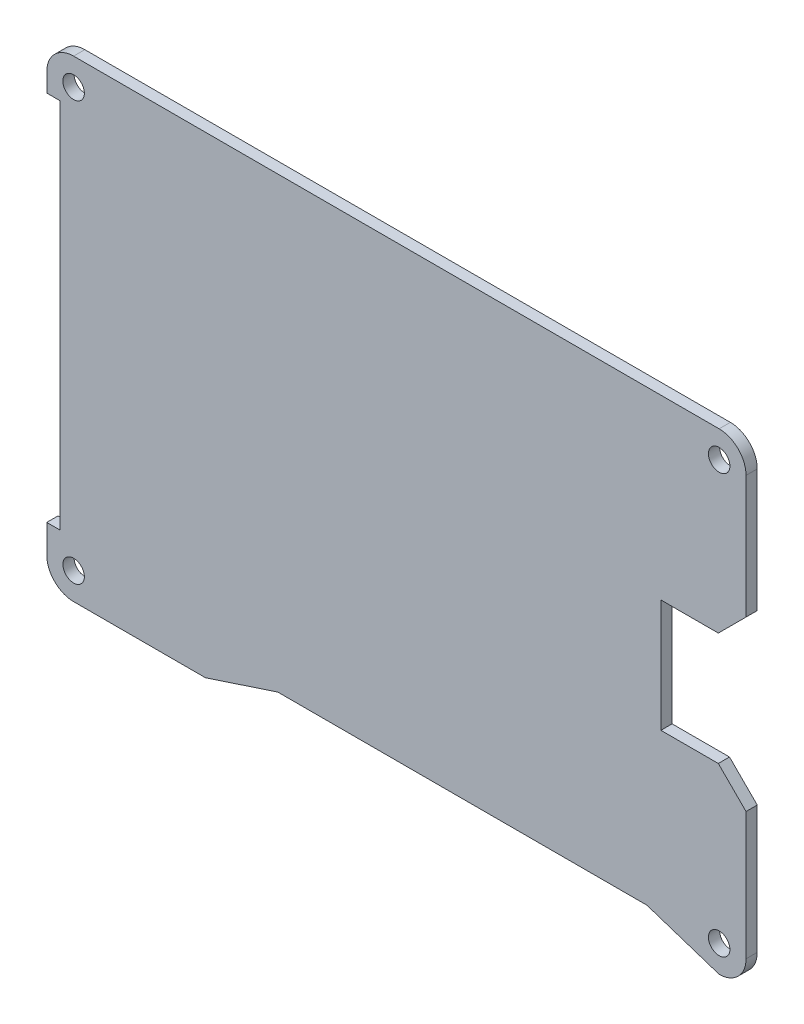
SolidWorks part; units mm, degrees
ref_plane "Front Plane" through (0, 0, 0) normal (0, 0, 1) x (1, 0, 0)
ref_plane "Top Plane" through (0, 0, 0) normal (0, 1, 0) x (1, 0, 0)
ref_plane "Right Plane" through (0, 0, 0) normal (1, 0, 0) x (0, 0, -1)
sketch "Sketch1" plane through (0, 0, 0) normal (0, 0, 1) x (1, 0, 0)
  line L5 (-301.9473, 132.8157) -> (-301.9473, 150.9704) construction
  line L6 (-305.7573, 154.7804) -> (-397.2471, 154.7804) construction
  line L7 (-401.0571, 150.9566) -> (-401.0571, 148.341) construction
  line L8 (-401.0571, 148.341) -> (-399.1521, 148.341) construction
  line L9 (-399.1521, 148.341) -> (-399.1521, 95.6449) construction
  line L10 (-399.1521, 95.6449) -> (-401.0571, 95.6449) construction
  line L11 (-401.0571, 95.6449) -> (-401.0571, 91.6593) construction
  line L12 (-397.2472, 87.8217) -> (-378.5565, 87.8217) construction
  line L13 (-378.5565, 87.8217) -> (-368.3165, 91.1883) construction
  line L14 (-368.3165, 91.1883) -> (-315.9973, 91.1883) construction
  line L15 (-315.9973, 91.1883) -> (-305.7573, 87.8217) construction
  line L16 (-301.9473, 91.6317) -> (-301.9473, 111.7465) construction
  line L17 (-301.9473, 133.5777) -> (-305.878, 129.6471)
  line L18 (-305.878, 129.6471) -> (-314.0123, 129.6471)
  line L19 (-314.0123, 129.6471) -> (-314.0123, 113.6451)
  line L20 (-314.0123, 113.6451) -> (-305.8779, 113.6451)
  line L21 (-305.8779, 113.6451) -> (-301.9473, 109.7145)
  line L22 (-301.9473, 133.5777) -> (-301.9473, 150.9704)
  line L23 (-305.7573, 154.7804) -> (-397.2471, 154.7804)
  line L24 (-401.0571, 150.9566) -> (-401.0571, 148.341)
  line L25 (-401.0571, 148.341) -> (-399.1521, 148.341)
  line L26 (-399.1521, 148.341) -> (-399.1521, 95.6449)
  line L27 (-399.1521, 95.6449) -> (-401.0571, 95.6449)
  line L28 (-401.0571, 95.6449) -> (-401.0571, 91.6593)
  line L29 (-397.2472, 87.8217) -> (-378.5565, 87.8217)
  line L30 (-378.5565, 87.8217) -> (-368.3165, 91.1883)
  line L31 (-368.3165, 91.1883) -> (-315.9973, 91.1883)
  line L32 (-315.9973, 91.1883) -> (-305.7573, 87.8217)
  line L33 (-301.9473, 91.6317) -> (-301.9473, 109.7145)
  circle A4 centre (-305.7573, 150.9704) radius 1.524
  circle A5 centre (-397.2471, 150.9704) radius 1.524
  circle A6 centre (-397.2472, 91.6317) radius 1.524
  circle A7 centre (-305.7573, 91.6317) radius 1.524
  arc A8 (-301.9473, 150.9704) -> (-305.7573, 154.7804) centre (-305.7573, 150.9704) ccw construction
  arc A9 (-397.2471, 154.7804) -> (-401.0571, 150.9566) centre (-397.2471, 150.9704) ccw construction
  arc A10 (-401.0571, 91.6593) -> (-397.2472, 87.8217) centre (-397.2472, 91.6317) ccw construction
  arc A11 (-305.7573, 87.8217) -> (-301.9473, 91.6317) centre (-305.7573, 91.6317) ccw construction
  arc A12 (-301.9473, 150.9704) -> (-305.7573, 154.7804) centre (-305.7573, 150.9704) ccw
  arc A13 (-397.2471, 154.7804) -> (-401.0571, 150.9566) centre (-397.2471, 150.9704) ccw
  arc A14 (-401.0571, 91.6593) -> (-397.2472, 87.8217) centre (-397.2472, 91.6317) ccw
  arc A15 (-305.7573, 87.8217) -> (-301.9473, 91.6317) centre (-305.7573, 91.6317) ccw
  dimension "D7" = 3.048
  dimension "D1" = 17.3927
  dimension "D2" = 3.9306
  dimension "D3" = 16.002
  dimension "D4" = 3.9307
  dimension "D5" = 8.1343
  dimension "D6" = 3.9307
extrude "Boss-Extrude1" add sketch "Sketch1" along normal blind 1.5875
sketch "Sketch2" [suppressed] plane through (0, 0, 1.5875) normal (0, 0, 1) x (1, 0, 0)
  line L0 (-351.5022, 121.301) -> (-351.5022, 159.401) construction
  line L1 (-301.9473, 150.9704) -> (-301.9473, 91.6317) construction
  line L2 (-401.0571, 121.301) -> (-301.9473, 121.301) construction
  line L3 (-351.5022, 83.201) -> (-351.5022, 159.401) construction
  line L4 (-361.0272, 83.201) -> (-361.0272, 159.401)
  line L5 (-341.9772, 83.201) -> (-341.9772, 159.401)
  line L6 (-361.0272, 154.7804) -> (-341.9772, 154.7804)
  line L7 (-305.7573, 154.7804) -> (-397.2471, 154.7804) construction
  line L8 (-361.0272, 91.6317) -> (-341.9772, 91.6317)
  circle A0 centre (-351.5022, 159.401) radius 3.175
  arc A1 (-361.0272, 83.201) -> (-341.9772, 83.201) centre (-351.5022, 83.201) ccw
  arc A2 (-341.9772, 159.401) -> (-361.0272, 159.401) centre (-351.5022, 159.401) ccw
  circle A3 centre (-351.5022, 83.201) radius 3.175
  point P13 (-351.5022, 121.301)
  line M11 (-305.7573, 154.7804) -> (-397.2471, 154.7804)
  line M21 (-368.3165, 91.1883) -> (-315.9973, 91.1883)
  dimension "D1" = 6.35
  dimension "D2" = 38.1
  dimension "D3" = 19.05
extrude "Boss-Extrude2" [suppressed] add sketch "Sketch2" against normal blind 1.5875 contours L5 A2 L4 A0 M11 | L4 A1 L5 A3 M21
sketch "Sketch6" [suppressed] plane through (0, 0, 1.5875) normal (0, 0, 1) x (1, 0, 0)
  line L0 (-386.6812, 159.8604) -> (-386.6812, 154.7804)
  line L1 (-305.7573, 154.7804) -> (-397.2471, 154.7804) construction
  line L2 (-379.8232, 159.8604) -> (-379.8232, 154.7804)
  line L3 (-379.8232, 154.7804) -> (-386.6812, 154.7804)
  line L4 (-316.3232, 159.8604) -> (-316.3232, 154.7804)
  line L5 (-316.3232, 154.7804) -> (-323.1812, 154.7804)
  line L6 (-323.1812, 154.7804) -> (-323.1812, 159.8604)
  line L7 (-383.2522, 159.8604) -> (-319.7522, 159.8604) construction
  line L8 (-351.5022, 159.8604) -> (-351.5022, 154.7804) construction
  line L10 (-351.5022, 154.7804) -> (-351.5022, 91.1883) construction
  line L11 (-368.3165, 91.1883) -> (-315.9973, 91.1883) construction
  line L12 (-354.9312, 83.5683) -> (-354.9312, 91.1883)
  line L13 (-354.9312, 91.1883) -> (-348.0732, 91.1883)
  line L14 (-348.0732, 91.1883) -> (-348.0732, 83.5683)
  circle A0 centre (-383.2522, 159.8604) radius 1.7843
  circle A1 centre (-319.7522, 159.8604) radius 1.7843
  circle A2 centre (-383.2522, 159.8604) radius 3.429
  circle A3 centre (-319.7522, 159.8604) radius 3.429
  circle A4 centre (-351.5022, 83.5683) radius 1.7145
  circle A5 centre (-351.5022, 83.5683) radius 3.429
  line M7 (-305.7573, 154.7804) -> (-397.2471, 154.7804)
  line M17 (-368.3165, 91.1883) -> (-315.9973, 91.1883)
  dimension "D2" = 6.858
  dimension "D3" = 3.5687
  dimension "D4" = 5.08
  dimension "D5" = 6.858
  dimension "D6" = 3.429
  dimension "D7" = 7.62
  dimension "D1" = 63.5
extrude "Boss-Extrude4" [suppressed] add sketch "Sketch6" against normal up to vertex contours A2 A0 | A2 L0 L2 M7 | A3 L6 L4 M7 | A3 A1 | A5 A4 | A5 L14 L12 M17 up to point (-368.3165, 91.1883, 0)
sketch "Sketch7" plane through (0, 0, 1.5875) normal (0, 0, 1) x (1, 0, 0)
  line L0 (-351.5022, 154.7804) -> (-351.5022, 91.1883) construction
  line L1 (-305.7573, 154.7804) -> (-397.2471, 154.7804) construction
  line L2 (-368.3165, 91.1883) -> (-315.9973, 91.1883) construction
  line L3 (-383.2522, 159.8604) -> (-319.7522, 159.8604) construction
  line L4 (-351.5022, 159.8604) -> (-351.5022, 154.7804) construction
  line L5 (-386.6812, 159.8604) -> (-386.6812, 154.7804)
  line L6 (-386.6812, 154.7804) -> (-379.8232, 154.7804)
  line L7 (-379.8232, 154.7804) -> (-379.8232, 159.8604)
  line L8 (-323.1812, 159.8604) -> (-323.1812, 154.7804)
  line L9 (-323.1812, 154.7804) -> (-316.3232, 154.7804)
  line L10 (-316.3232, 154.7804) -> (-316.3232, 159.8604)
  line L11 (-354.9312, 83.6604) -> (-354.9312, 91.1883)
  line L12 (-354.9312, 91.1883) -> (-348.0732, 91.1883)
  line L13 (-348.0732, 91.1883) -> (-348.0732, 83.6604)
  circle A0 centre (-383.2522, 159.8604) radius 1.7843
  circle A1 centre (-319.7522, 159.8604) radius 1.7843
  circle A2 centre (-383.2522, 159.8604) radius 3.429
  circle A3 centre (-319.7522, 159.8604) radius 3.429
  circle A4 centre (-351.5022, 83.6604) radius 1.7843
  circle A5 centre (-351.5022, 83.6604) radius 3.429
  line M5 (-305.7573, 154.7804) -> (-397.2471, 154.7804)
  line M15 (-368.3165, 91.1883) -> (-315.9973, 91.1883)
  dimension "D1" = 3.5687
  dimension "D3" = 6.858
  dimension "D2" = 63.5
  dimension "D4" = 5.08
  dimension "D5" = 76.2
extrude "Boss-Extrude5" [suppressed] add sketch "Sketch7" against normal up to vertex contours A2 L5 L7 M5 | A2 A0 | A3 L8 L10 M5 | A3 A1 | A5 A4 | A5 L13 L11 M15 up to point (-315.9973, 91.1883, 0)
